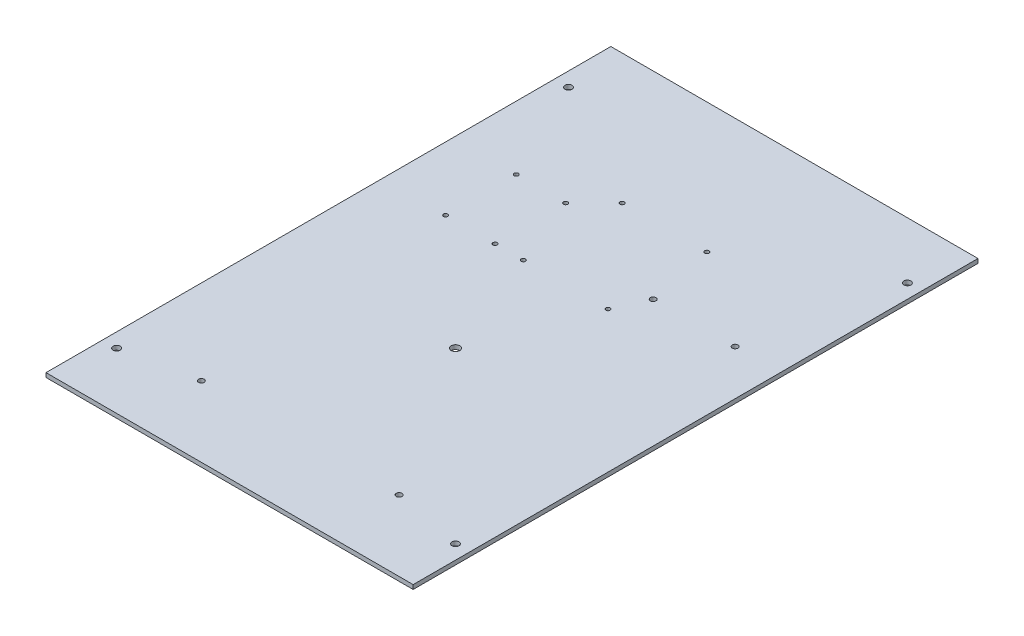
SolidWorks part; units mm, degrees
ref_plane "Front Plane" through (0, 0, 0) normal (0, 0, 1) x (1, 0, 0)
ref_plane "Top Plane" through (0, 0, 0) normal (0, 1, 0) x (1, 0, 0)
ref_plane "Right Plane" through (0, 0, 0) normal (1, 0, 0) x (0, 0, -1)
sketch "Sketch1" plane through (0, 0, 0) normal (0, 1, 0) x (1, 0, 0)
  line L1 (0, 0) -> (260, 0)
  line L2 (0, 0) -> (0, 400)
  line L3 (0, 400) -> (260, 400)
  line L4 (260, 0) -> (260, 400)
  circle A0 centre (130, 160) radius 3
  circle A2 centre (100, 238) radius 1.5
  circle A3 centre (160, 238) radius 1.5
  circle A4 centre (160, 308) radius 1.5
  circle A5 centre (100, 308) radius 1.5
  circle A6 centre (80, 238) radius 1.5
  circle A7 centre (45, 238) radius 1.5
  circle A8 centre (45, 288) radius 1.5
  circle A9 centre (80, 288) radius 1.5
  circle A10 centre (170, 260) radius 2
  circle A11 centre (228, 260) radius 2
  circle A12 centre (10, 360) radius 2.5
  circle A13 centre (250, 360) radius 2.5
  circle A14 centre (250, 40) radius 2.5
  circle A15 centre (10, 40) radius 2.5
  circle A16 centre (200, 50) radius 2
  circle A17 centre (60, 50) radius 2
  point P7 (0, 0)
  point P8 (0, 0)
  point P28 (80, 288)
  point P33 (0, 0)
  point P41 (0, 0)
  point P43 (0, 0)
  point P44 (0, 0)
  point P45 (0, 0)
  point P46 (0, 0)
  point P47 (0, 0)
  point P48 (0, 0)
  point P49 (0, 0)
  point P50 (0, 0)
  point P51 (0, 0)
  point P52 (0, 0)
  point P53 (0, 0)
  dimension "D5" = 6
  dimension "D15" = 5
  dimension "D18" = 5
  dimension "D19" = 5
  dimension "D20" = 5
  dimension "D27" = 4
  dimension "D35" = 3
  dimension "D36" = 4
  dimension "D2" = 400
  dimension "D3" = 260
  dimension "D4" = 240
  dimension "D6" = 58
  dimension "D7" = 78
  dimension "D8" = 60
  dimension "D9" = 70
  dimension "D10" = 22
  dimension "D12" = 35
  dimension "D13" = 50
  dimension "D14" = 30
  dimension "D16" = 10
  dimension "D17" = 40
  dimension "D21" = 10
  dimension "D22" = 40
  dimension "D23" = 40
  dimension "D24" = 10
  dimension "D25" = 40
  dimension "D26" = 10
  dimension "D28" = 60
  dimension "D29" = 50
  dimension "D31" = 60
  dimension "D32" = 50
  dimension "D33" = 130
  dimension "D11" = 50
  dimension "D34" = 32
extrude "Boss-Extrude1" add sketch "Sketch1" along normal blind 3 contours L1 L4 L3 L2 A11 A10 A9 A8 A7 A6 A5 A4 A3 A2 A0 region at (130.0017, 0, -199.9956)
equation "\"D33@Sketch1\"=\"D3@Sketch1\"/2"
equation "\"D18@Sketch1\"=\"D15@Sketch1\""
equation "\"D19@Sketch1\"=\"D15@Sketch1\""
equation "\"D20@Sketch1\"=\"D15@Sketch1\""
